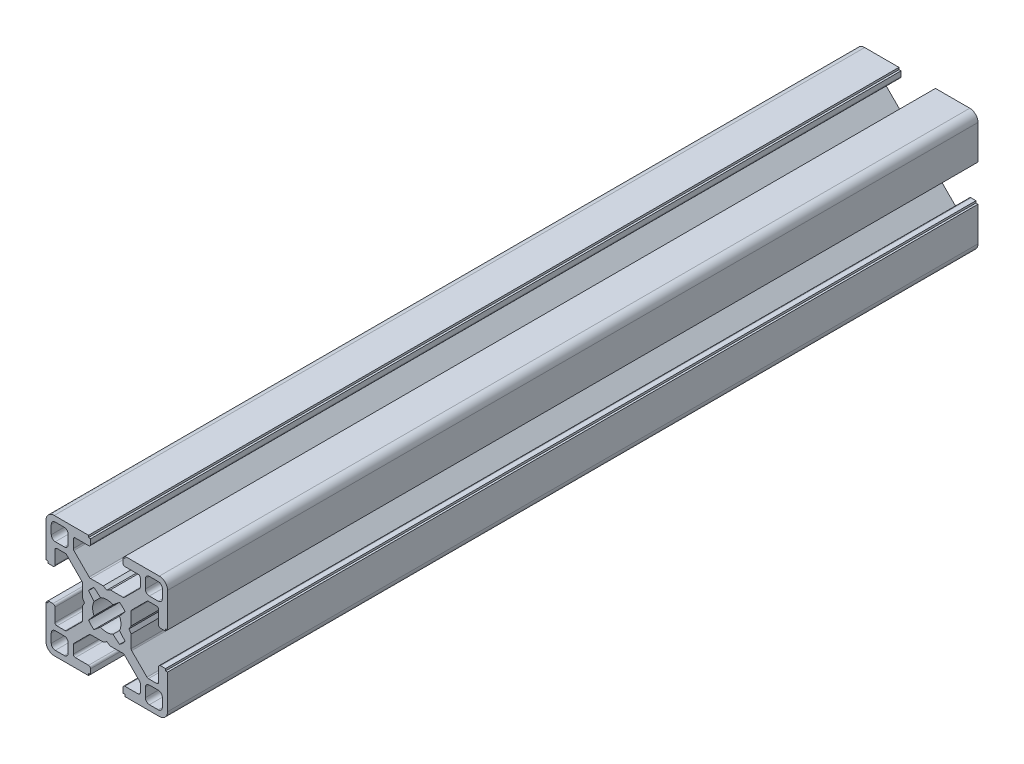
SolidWorks part; units mm, degrees
ref_plane "Front Plane" through (0, 0, 0) normal (0, 0, 1) x (1, 0, 0)
ref_plane "Top Plane" through (0, 0, 0) normal (0, 1, 0) x (1, 0, 0)
ref_plane "Right Plane" through (0, 0, 0) normal (1, 0, 0) x (0, 0, -1)
sketch "Sketch1" plane through (0, 0, 0) normal (0, 0, 1) x (1, 0, 0)
  line L0 (-15, 0) -> (15, 0) construction
  line L1 (0, -15) -> (0, 15) construction
  line L2 (-4.5, 15) -> (4.5, 15) construction
  line L3 (-4, -15) -> (4, -15) construction
  line L4 (-4.5, 15) -> (-4.5, 14.5)
  line L5 (-4.5, 14.5) -> (-4, 14.5)
  line L6 (-4, 14.5) -> (-4, 13.29)
  line L7 (-4.5, 12.79) -> (-7.7675, 12.79)
  line L8 (-8.2675, 12.29) -> (-8.2675, 10.2707)
  line L9 (-8.1211, 9.9171) -> (-4.3504, 6.1464)
  line L10 (-3.9968, 6) -> (0, 6)
  line L11 (0, 0) -> (-15, 15) construction
  line L12 (-4.5, 15) -> (-12.968, 15)
  line L14 (-12.705, 9.5135) -> (-10.5135, 9.5135)
  line L15 (-13.705, 10.5135) -> (-13.705, 12.705)
  line L16 (-12.705, 13.705) -> (-10.5135, 13.705)
  line L17 (-9.5135, 10.5135) -> (-9.5135, 12.705)
  line L18 (-13.705, 9.5135) -> (-9.5135, 13.705) construction
  line L19 (-13.705, 13.705) -> (-9.5135, 9.5135) construction
  line L20 (-3.1568, 4.5038) -> (-1.5303, 3.1477) construction
  line L21 (-4.5038, 3.1568) -> (-3.1477, 1.5303) construction
  line L22 (-6, 3.9968) -> (-6, 0)
  line L23 (-9.9171, 8.1211) -> (-6.1464, 4.3504)
  line L24 (-15, 4.5) -> (-15, 12.968)
  line L25 (-12.29, 8.2675) -> (-10.2707, 8.2675)
  line L26 (-12.79, 4.5) -> (-12.79, 7.7675)
  line L27 (-14.5, 4) -> (-13.29, 4)
  line L28 (-14.5, 4.5) -> (-14.5, 4)
  line L29 (-15, 4.5) -> (-14.5, 4.5)
  circle A0 centre (0, 0) radius 3.5
  arc A1 (-12.968, 15) -> (-15, 12.968) centre (-12.968, 12.968) ccw
  circle A2 centre (0, 0) radius 5.5 construction
  arc A3 (-10.5135, 9.5135) -> (-9.5135, 10.5135) centre (-10.5135, 10.5135) ccw
  arc A4 (-13.705, 12.705) -> (-12.705, 13.705) centre (-12.705, 12.705) cw
  arc A5 (-10.5135, 13.705) -> (-9.5135, 12.705) centre (-10.5135, 12.705) cw
  arc A6 (-12.705, 9.5135) -> (-13.705, 10.5135) centre (-12.705, 10.5135) cw
  arc A7 (-12.79, 4.5) -> (-13.29, 4) centre (-13.29, 4.5) cw
  arc A8 (-12.29, 8.2675) -> (-12.79, 7.7675) centre (-12.29, 7.7675) ccw
  arc A9 (-9.9171, 8.1211) -> (-10.2707, 8.2675) centre (-10.2707, 7.7675) ccw
  arc A10 (-6, 3.9968) -> (-6.1464, 4.3504) centre (-6.5, 3.9968) ccw
  arc A11 (-4.3504, 6.1464) -> (-3.9968, 6) centre (-3.9968, 6.5) ccw
  arc A12 (-4, 13.29) -> (-4.5, 12.79) centre (-4.5, 13.29) cw
  arc A13 (-7.7675, 12.79) -> (-8.2675, 12.29) centre (-7.7675, 12.29) ccw
  arc A14 (-8.2675, 10.2707) -> (-8.1211, 9.9171) centre (-7.7675, 10.2707) ccw
  point P4 (0, 0)
  point P8 (0, 0)
  point P13 (0, 15)
  point P15 (0, -15)
  point P16 (0, 6)
  point P23 (-11.6092, 11.6093)
  point P26 (0, 6)
  point P62 (-12.79, 4)
  point P65 (-12.79, 8.2675)
  point P68 (-10.0636, 8.2675)
  point P71 (-6, 4.2039)
  point P74 (-4.2039, 6)
  point P77 (-4, 12.79)
  point P80 (-8.2675, 12.79)
  point P83 (-8.2675, 10.0636)
  dimension "Center Hole Diameter" = 7
  dimension "D11" = 2.032
  dimension "D9" = 11
  dimension "D13" = 1
  dimension "D14" = 0.5
  dimension "Rail Height" = 30
  dimension "Rail Width" = 30
  dimension "T-Slot Width" = 8
  dimension "T-Slot Depth" = 9
  dimension "D1" = 9
  dimension "D2" = 45
  dimension "D3" = 8
  dimension "D4" = 2.21
  dimension "D5" = 16.535
  dimension "D7" = 2.54
  dimension "D6" = 1.295
  dimension "D8" = 1.246
  dimension "D10" = 10.36
  dimension "D12" = 1.905
sketch "Sketch2" plane through (0, 0, 0) normal (1, 0, 0) x (0, 0, -1)
  line L0 (-76.2, 0) -> (76.2, 0) construction
  line L2 (0, -15) -> (0, 15) construction
  line L3 (0, -15) -> (0, 15) construction
  line L4 (-76.2, -15) -> (-76.2, 15) construction
  line L5 (76.2, -15) -> (76.2, 15) construction
  point P0 (-38.7, 0)
  point P3 (0, 0)
  point P4 (38.7, 0)
  point P12 (-76.2, 0)
  point P14 (76.2, 0)
  dimension "Length" = 152.4
  dimension "D1" = 37.5
sketch "Sketch3" plane through (0, 0, 0) normal (0, 0, 1) x (1, 0, 0)
  line L0 (-4.5038, 3.1568) -> (-3.1477, 1.5303)
  line L1 (0, 3.5) -> (0, 5.5)
  line L2 (-5.5, 0) -> (-3.5, 0)
  line L7 (-6, 3.9968) -> (-6, 0) construction
  line L31 (-9.9171, 8.1211) -> (-6.1464, 4.3504) construction
  line L117 (-12.29, 8.2675) -> (-10.2707, 8.2675) construction
  line L118 (-12.79, 4.5) -> (-12.79, 7.7675) construction
  line L157 (-12.705, 9.5135) -> (-10.5135, 9.5135)
  line L158 (-9.5135, 10.5135) -> (-9.5135, 12.705)
  line L163 (-10.5135, 13.705) -> (-12.705, 13.705)
  line L164 (-13.705, 12.705) -> (-13.705, 10.5135)
  line L165 (-12.705, 9.5135) -> (-10.5135, 9.5135)
  line L166 (-9.5135, 10.5135) -> (-9.5135, 12.705)
  line L167 (-10.5135, 13.705) -> (-12.705, 13.705)
  line L168 (-13.705, 12.705) -> (-13.705, 10.5135)
  line L169 (-14.5, 4) -> (-13.29, 4) construction
  line L170 (-14.5, 4.5) -> (-14.5, 4) construction
  line L171 (-15, 4.5) -> (-14.5, 4.5) construction
  line L172 (-15, 4.5) -> (-15, 12.968) construction
  line L173 (-4.5, 15) -> (-12.968, 15) construction
  line L174 (-4.5, 15) -> (-4.5, 14.5) construction
  line L175 (-4.5, 14.5) -> (-4, 14.5) construction
  line L176 (-4, 14.5) -> (-4, 13.29) construction
  line L177 (-4.5, 12.79) -> (-7.7675, 12.79) construction
  line L178 (-8.2675, 12.29) -> (-8.2675, 10.2707) construction
  line L179 (-8.1211, 9.9171) -> (-4.3504, 6.1464) construction
  line L180 (-3.9968, 6) -> (0, 6) construction
  line L181 (-6, 3.9968) -> (-6, 0.866)
  line L182 (-9.9171, 8.1211) -> (-6.1464, 4.3504)
  line L183 (-12.29, 8.2675) -> (-10.2707, 8.2675)
  line L184 (-12.79, 4.5) -> (-12.79, 7.7675)
  line L185 (-14.5, 4) -> (-13.29, 4)
  line L186 (-14.5, 4.5) -> (-14.5, 4)
  line L187 (-15, 4.5) -> (-14.5, 4.5)
  line L188 (-15, 4.5) -> (-15, 12.968)
  line L189 (-4.5, 15) -> (-12.968, 15)
  line L190 (-4.5, 15) -> (-4.5, 14.5)
  line L191 (-4.5, 14.5) -> (-4, 14.5)
  line L192 (-4, 14.5) -> (-4, 13.29)
  line L193 (-4.5, 12.79) -> (-7.7675, 12.79)
  line L194 (-8.2675, 12.29) -> (-8.2675, 10.2707)
  line L195 (-8.1211, 9.9171) -> (-4.3504, 6.1464)
  line L196 (-3.9968, 6) -> (-0.866, 6)
  line L197 (-0.866, 6) -> (0, 5.5)
  line L198 (0, -15) -> (0, 15) construction
  line L199 (0, 0) -> (-15, 15) construction
  line L200 (0, 0) -> (-15, 15) construction
  line L201 (-3.1568, 4.5038) -> (-1.5303, 3.1477) construction
  line L202 (-3.1568, 4.5038) -> (-1.5303, 3.1477)
  line L203 (-6, 0.866) -> (-5.5, 0)
  line L204 (-15, 0) -> (15, 0) construction
  line L205 (-15, 0) -> (15, 0) construction
  line L206 (0, -15) -> (0, 15) construction
  arc A0 (-3.5, 0) -> (-3.1477, 1.5303) centre (0, 0) cw
  arc A10 (-6, 3.9968) -> (-6.1464, 4.3504) centre (-6.5, 3.9968) ccw construction
  circle A16 centre (0, 0) radius 3.5
  arc A18 (0, 3.5) -> (-1.5303, 3.1477) centre (0, 0) ccw
  arc A20 (-9.9171, 8.1211) -> (-10.2707, 8.2675) centre (-10.2707, 7.7675) ccw construction
  arc A22 (-12.29, 8.2675) -> (-12.79, 7.7675) centre (-12.29, 7.7675) ccw construction
  arc A28 (-13.29, 4) -> (-12.79, 4.5) centre (-13.29, 4.5) ccw construction
  arc A29 (-10.5135, 9.5135) -> (-9.5135, 10.5135) centre (-10.5135, 10.5135) ccw
  arc A30 (-9.5135, 12.705) -> (-10.5135, 13.705) centre (-10.5135, 12.705) ccw
  arc A31 (-12.705, 13.705) -> (-13.705, 12.705) centre (-12.705, 12.705) ccw
  arc A32 (-13.705, 10.5135) -> (-12.705, 9.5135) centre (-12.705, 10.5135) ccw
  arc A33 (-10.5135, 9.5135) -> (-9.5135, 10.5135) centre (-10.5135, 10.5135) ccw
  arc A34 (-9.5135, 12.705) -> (-10.5135, 13.705) centre (-10.5135, 12.705) ccw
  arc A35 (-12.705, 13.705) -> (-13.705, 12.705) centre (-12.705, 12.705) ccw
  arc A36 (-13.705, 10.5135) -> (-12.705, 9.5135) centre (-12.705, 10.5135) ccw
  arc A37 (-12.968, 15) -> (-15, 12.968) centre (-12.968, 12.968) ccw construction
  arc A38 (-4.5, 12.79) -> (-4, 13.29) centre (-4.5, 13.29) ccw construction
  arc A39 (-7.7675, 12.79) -> (-8.2675, 12.29) centre (-7.7675, 12.29) ccw construction
  arc A40 (-8.2675, 10.2707) -> (-8.1211, 9.9171) centre (-7.7675, 10.2707) ccw construction
  arc A41 (-4.3504, 6.1464) -> (-3.9968, 6) centre (-3.9968, 6.5) ccw construction
  arc A42 (-6, 3.9968) -> (-6.1464, 4.3504) centre (-6.5, 3.9968) ccw
  arc A43 (-9.9171, 8.1211) -> (-10.2707, 8.2675) centre (-10.2707, 7.7675) ccw
  arc A44 (-12.29, 8.2675) -> (-12.79, 7.7675) centre (-12.29, 7.7675) ccw
  arc A45 (-13.29, 4) -> (-12.79, 4.5) centre (-13.29, 4.5) ccw
  arc A46 (-12.968, 15) -> (-15, 12.968) centre (-12.968, 12.968) ccw
  arc A47 (-4.5, 12.79) -> (-4, 13.29) centre (-4.5, 13.29) ccw
  arc A48 (-7.7675, 12.79) -> (-8.2675, 12.29) centre (-7.7675, 12.29) ccw
  arc A49 (-8.2675, 10.2707) -> (-8.1211, 9.9171) centre (-7.7675, 10.2707) ccw
  arc A50 (-4.3504, 6.1464) -> (-3.9968, 6) centre (-3.9968, 6.5) ccw
  circle A51 centre (0, 0) radius 5.5 construction
  arc A52 (-3.1568, 4.5038) -> (-4.5038, 3.1568) centre (0, 0) ccw
  dimension "D3" = 60
  dimension "D4" = 60
  dimension "D1" = 0
  dimension "D2" = 0
extrude "Boss-Extrude1" add sketch "Sketch3" along normal mid plane 200
pattern_circular "CirPattern1" count 4 over 360 about axis through (0, 0, 76.2) along (0, 0, -1) of "Boss-Extrude1"
ref_plane "Contact Plane1" through (15, 0, 0) normal (1, 0, 0) x (0, 0, -1)
ref_plane "Contact Plane2" through (0, -15, 0) normal (0, 1, 0) x (1, 0, 0)
ref_plane "Contact Plane3" through (-15, 0, 0) normal (1, 0, 0) x (0, 0, -1)
ref_plane "Contact Plane4" through (0, 15, 0) normal (0, 1, 0) x (1, 0, 0)
equation "\"D1@Sketch2\" = \"Rail Height@Sketch1\" * 1.25"
equation "\"D1@Sketch1\"=\"T-Slot Width@Sketch1\"+1mm"
equation "\"D3@Sketch1\"=\"T-Slot Width@Sketch1\""
equation "\"D1@Boss-Extrude1\"=\"Width\""
equation "\"Width\" = 200mm"
